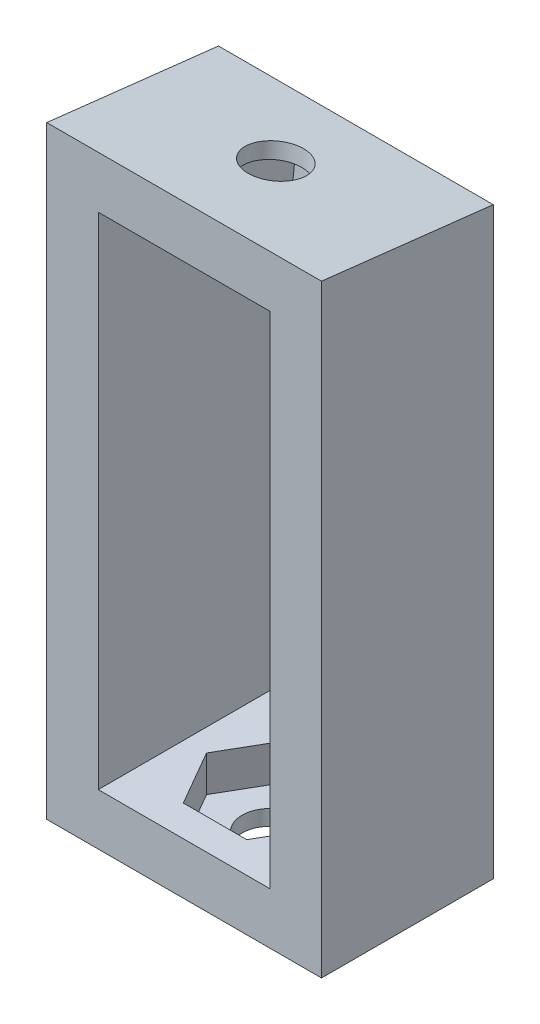
SolidWorks part; units mm, degrees
ref_plane "Front Plane" through (0, 0, 0) normal (0, 0, 1) x (1, 0, 0)
ref_plane "Top Plane" through (0, 0, 0) normal (0, 1, 0) x (1, 0, 0)
ref_plane "Right Plane" through (0, 0, 0) normal (1, 0, 0) x (0, 0, -1)
sketch "Sketch1" plane through (0, 0, 0) normal (1, 0, 0) x (0, 0, -1)
  line L0 (-10, 34) -> (-10, 35.1394)
  line L1 (0, 0) -> (-10, 0)
  line L2 (0, 0) -> (0, 34)
  line L3 (0, 34) -> (-10, 34)
  line L4 (-10, 0) -> (-10, 34)
  line L5 (-10, 35.1394) -> (0, 34)
  dimension "D1" = 6.5
  dimension "D2" = 10
  dimension "D3" = 34
extrude "Boss-Extrude1" add sketch "Sketch1" along normal blind 3 contours L4 L1 L2 L3 | L5 L0 L3 region at (0, 34.3798, 6.6667) region at (0, 17, 5)
ref_plane "Plane1" through (13, 0, 0) normal (1, 0, 0) x (0, 0, -1)
sketch "Sketch2" plane through (13, 0, 0) normal (1, 0, 0) x (0, 0, -1)
  line L0 (0, 0) -> (-10, 0) construction
  line L1 (0, 0) -> (0, 34) construction
  line L2 (-10, 0) -> (-10, 34) construction
  line L3 (-10, 34) -> (-10, 35.1394) construction
  line L4 (-10, 35.1394) -> (0, 34) construction
  line L5 (0, 34) -> (-10, 34) construction
  line L6 (0, 0) -> (-10, 0)
  line L7 (0, 0) -> (0, 34)
  line L8 (-10, 0) -> (-10, 34)
  line L9 (-10, 34) -> (-10, 35.1394)
  line L10 (-10, 35.1394) -> (0, 34)
  line L11 (0, 34) -> (-10, 34)
  line L12 (-10, 32.1199) -> (0, 30.9806)
  line L13 (-10, 3) -> (0, 3)
  dimension "D1" = 3
  dimension "D2" = 3
extrude "Boss-Extrude2" add sketch "Sketch2" along normal blind 3 separate body contours L12 L8 L6 L7 | L8 L12 L7 L11 | L11 L10 L9 | L6 L8 L9 L10 L7 region at (13, 17.277, 5.0333) region at (13, 32.7531, 4.6124) region at (13, 34.3798, 6.6667)
extrude "Boss-Extrude3" add sketch "Sketch2<4>" against normal up to surface (10 mm away) contours L13 L8 L6 L7 | L8 L12 L7 L11 | L11 L10 L9 region at (13, 1.5, 5) region at (13, 32.7531, 4.6124) region at (13, 34.3798, 6.6667) up to face at (3, 17.2848, 5)
sketch "Sketch2<4>" plane through (13, 0, 0) normal (1, 0, 0) x (0, 0, -1) same geometry as "Sketch2"
sketch "Sketch5" plane through (0, 3, 0) normal (0, 1, 0) x (1, 0, 0)
  line L0 (8, -10) -> (8, 0) construction
  line L1 (3, -10) -> (13, -10) construction
  line L2 (3, 0) -> (13, 0) construction
  line L4 (6.1525, -1.8) -> (4.305, -5)
  line L5 (4.305, -5) -> (6.1525, -8.2)
  line L6 (6.1525, -8.2) -> (9.8475, -8.2)
  line L7 (9.8475, -8.2) -> (11.695, -5)
  line L8 (11.695, -5) -> (9.8475, -1.8)
  line L9 (9.8475, -1.8) -> (6.1525, -1.8)
  circle A0 centre (8, -5) radius 1.625
  circle A1 centre (8, -5) radius 3.2 construction
  dimension "D1" = 3.25
  dimension "D2" = 6.4
sketch "Sketch6" plane through (0, 30.5836, -3.4846) normal (0, -0.9936, 0.1132) x (1, 0, 0)
  line L0 (8, 13.5718) -> (8, 3.5071) construction
  line L1 (3, 13.5718) -> (13, 13.5718) construction
  line L2 (3, 3.5071) -> (13, 3.5071) construction
  line L4 (9.8475, 5.3395) -> (11.695, 8.5395)
  line L5 (11.695, 8.5395) -> (9.8475, 11.7395)
  line L6 (9.8475, 11.7395) -> (6.1525, 11.7395)
  line L7 (6.1525, 11.7395) -> (4.305, 8.5395)
  line L8 (4.305, 8.5395) -> (6.1525, 5.3395)
  line L9 (6.1525, 5.3395) -> (9.8475, 5.3395)
  circle A0 centre (8, 8.5395) radius 1.625
  circle A1 centre (8, 8.5395) radius 3.2 construction
  dimension "D1" = 3.25
  dimension "D2" = 6.4
extrude "Cut-Extrude3" cut sketch "Sketch6" against normal blind 2.1 contours L8 L9 L4 L5 L6 L7 A0 | A0 region at (8, 31.1991, 1.9177) region at (8, 31.5503, 5)
extrude "Cut-Extrude4" cut sketch "Sketch6<3>" against normal through all contours A0 region at (8, 31.5503, 5)
sketch "Sketch6<3>" plane through (0, 30.5836, -3.4846) normal (0, -0.9936, 0.1132) x (1, 0, 0) same geometry as "Sketch6"
extrude "Cut-Extrude5" cut sketch "Sketch5" against normal blind 2.1
extrude "Cut-Extrude6" cut sketch "Sketch5<4>" against normal through all contours A0 region at (8, 3, 5)
sketch "Sketch5<4>" plane through (0, 3, 0) normal (0, 1, 0) x (1, 0, 0) same geometry as "Sketch5"
